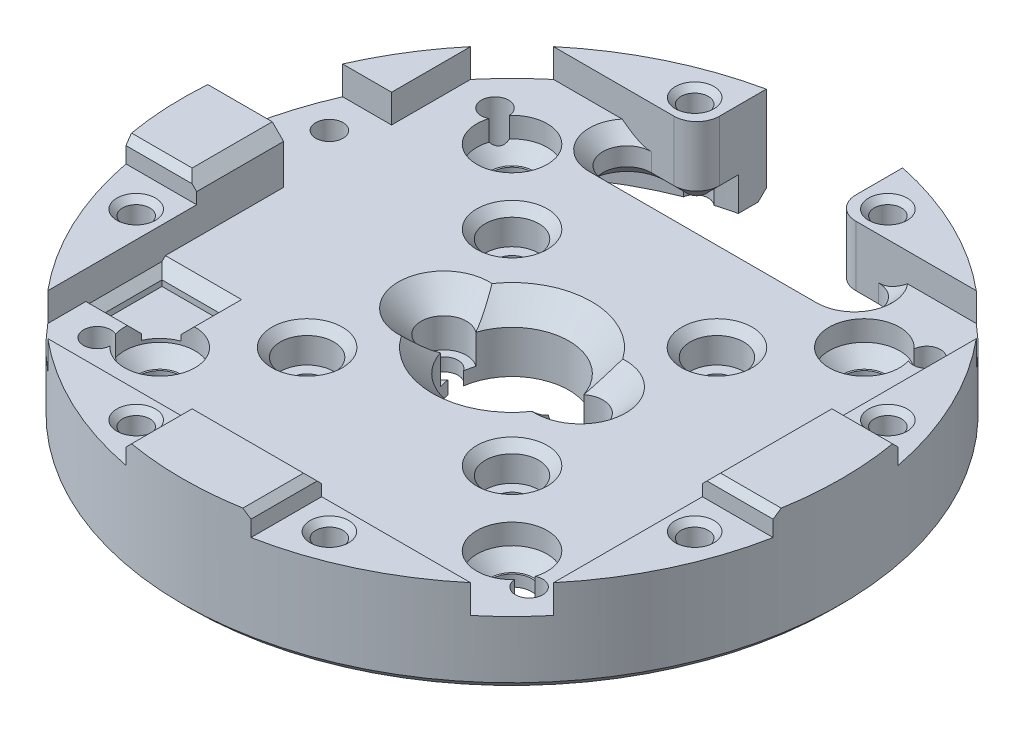
SolidWorks part; units mm, degrees
ref_plane "Front Plane" through (0, 0, 0) normal (0, 0, 1) x (1, 0, 0)
ref_plane "Top Plane" through (0, 0, 0) normal (0, 1, 0) x (1, 0, 0)
ref_plane "Right Plane" through (0, 0, 0) normal (1, 0, 0) x (0, 0, -1)
sketch "Sketch1" plane through (0, 0, 0) normal (0, 1, 0) x (1, 0, 0)
  circle A0 centre (0, 0) radius 8.75
  arc A1 (-4.9531, -0.683) -> (4.9531, -0.683) centre (0, 0) ccw
  circle A2 centre (0, 0) radius 6 construction
  arc A3 (-4.9531, 0.683) -> (-4.9531, -0.683) centre (-6, 0) ccw
  arc A4 (4.9531, -0.683) -> (4.9531, 0.683) centre (6, 0) ccw
  arc A5 (4.9531, 0.683) -> (-4.9531, 0.683) centre (0, 0) ccw
  dimension "D1" = 17.5
  dimension "D2" = 10
  dimension "D3" = 2.5
  dimension "D4" = 12
extrude "Boss-Extrude1" add sketch "Sketch1" along normal blind 1.75
sketch "Sketch2" plane through (0, 1.75, 0) normal (0, 1, 0) x (1, 0, 0)
  circle A0 centre (-6, 0) radius 2
  circle A1 centre (6, 0) radius 2
  dimension "D1" = 4
extrude "Cut-Extrude1" cut sketch "Sketch2" against normal blind 0.6
sketch "Sketch3" plane through (0, 1.75, 0) normal (0, -1, 0) x (1, 0, 0)
  line L0 (-12.0837, 0) -> (12.0837, 0) construction
  line L1 (-19, -17.5) -> (19, -17.5) construction
  line L2 (-19, -17.5) -> (-19, 17.5) construction
  line L3 (-19, 17.5) -> (19, 17.5) construction
  line L4 (19, -17.5) -> (19, 17.5) construction
  line L5 (-19, -17.5) -> (19, 17.5) construction
  line L6 (-19, 17.5) -> (19, -17.5) construction
  line L11 (-23.4352, -20.7052) -> (23.4352, 20.7052) construction
  line L12 (-23.4352, 20.7052) -> (23.4352, -20.7052) construction
  line L13 (0, 12.2133) -> (0, -11.1132) construction
  circle A0 centre (19, 17.5) radius 1.2
  circle A1 centre (19, -17.5) radius 1.2
  circle A2 centre (-19, -17.5) radius 1.2
  circle A3 centre (-19, 17.5) radius 1.2
  arc A8 (-4.75, -1.5612) -> (4.75, -1.5612) centre (0, 0) ccw
  circle A9 centre (0, 0) radius 5 construction
  arc A10 (-4.75, 1.5612) -> (-4.75, -1.5612) centre (-6, 0) ccw
  arc A11 (4.75, -1.5612) -> (4.75, 1.5612) centre (6, 0) ccw
  circle A12 centre (0, 0) radius 29
  arc A14 (-4.75, 1.5612) -> (-4.75, -1.5612) centre (-6, 0) ccw construction
  arc A15 (4.75, 1.5612) -> (-4.75, 1.5612) centre (0, 0) ccw
  point P0 (0, 0)
  point P6 (0, 0)
  dimension "D3" = 2.4
  dimension "D4" = 58
  dimension "D1" = 35
  dimension "D2" = 38
extrude "Boss-Extrude2" add sketch "Sketch3" against normal blind 6.5
sketch "Sketch4" plane through (0, 8.25, 0) normal (0, 1, 0) x (1, 0, 0)
  line L1 (-22.25, 22.25) -> (22.25, 22.25)
  line L2 (-22.25, 22.25) -> (-22.25, -22.25)
  line L3 (-22.25, -22.25) -> (22.25, -22.25)
  line L4 (22.25, 22.25) -> (22.25, -22.25)
  line L5 (-22.25, 22.25) -> (22.25, -22.25) construction
  line L6 (-22.25, -22.25) -> (22.25, 22.25) construction
  point P0 (0, 0)
  dimension "D1" = 44.5
  dimension "D2" = 44.5
extrude "Cut-Extrude2" cut sketch "Sketch4" against normal blind 2.5
chamfer "Chamfer1" distance 0.5 angle 45 1 edges at (0, 0, 8.75)
chamfer "Chamfer2" distance 2 angle 45 4 edges at (0, 5.75, 5) (8, 5.75, 0) (0, 5.75, -5) (-8, 5.75, 0)
sketch "Sketch10" plane through (0, 1.75, 0) normal (0, -1, 0) x (1, 0, 0)
  circle A0 centre (0, 0) radius 26.6
  circle A1 centre (0, 0) radius 29
  circle A2 centre (0, 0) radius 29 construction
  dimension "D1" = 53.2
extrude "Boss-Extrude3" add sketch "Sketch10" along normal blind 1.75
sketch "Sketch5" plane through (0, 5.75, 0) normal (0, 1, 0) x (1, 0, 0)
  line L0 (15.4998, -15.4998) -> (-15.4998, 15.4998) construction
  line L1 (15.4998, 15.4998) -> (-15.4998, -15.4998) construction
  line L2 (0, 17.5033) -> (0, -11.3042) construction
  circle A0 centre (0, 0) radius 21.92 construction
  circle A1 centre (-15.4998, 15.4998) radius 1.75
  circle A2 centre (15.4998, 15.4998) radius 1.75
  circle A3 centre (15.4998, -15.4998) radius 1.75
  circle A4 centre (-15.4998, -15.4998) radius 1.75
  dimension "D1" = 43.84
  dimension "D3" = 3.5
  dimension "D2" = 45
extrude "Cut-Extrude3" cut sketch "Sketch5" against normal through all
sketch "Sketch7" plane through (0, 8.25, 0) normal (0, 1, 0) x (1, 0, 0)
  line L1 (-6, 42.3425) -> (6, 42.3425)
  line L2 (-6, 42.3425) -> (-6, 18)
  line L3 (-6, 18) -> (6, 18)
  line L4 (6, 42.3425) -> (6, 18)
  line L5 (-6, 42.3425) -> (6, 18) construction
  line L6 (-6, 18) -> (6, 42.3425) construction
  point P0 (0, 30.1713)
  point P5 (0, 0)
  point P7 (0, 24.1805)
  dimension "D1" = 12
  dimension "D2" = 18
extrude "Cut-Extrude5" cut sketch "Sketch7" against normal blind 12
sketch "Sketch11" plane through (0, 5.75, 0) normal (0, 1, 0) x (1, 0, 0)
  line L0 (0, 0) -> (15.4998, 15.4998) construction
  line L1 (0, 0) -> (-15.4998, 15.4998) construction
  line L2 (0, 0) -> (-15.4998, -15.4998) construction
  line L3 (0, 0) -> (15.4998, -15.4998) construction
  circle A0 centre (0, 0) radius 12.75 construction
  circle A1 centre (-9.0156, 9.0156) radius 2.35
  circle A2 centre (9.0156, 9.0156) radius 2.35
  circle A3 centre (9.0156, -9.0156) radius 2.35
  circle A4 centre (-9.0156, -9.0156) radius 2.35
  point P19 (15.4998, 15.4998)
  point P21 (-15.4998, 15.4998)
  point P23 (15.4998, -15.4998)
  point P25 (-15.4998, -15.4998)
  dimension "D1" = 25.5
  dimension "D2" = 4.7
extrude "Cut-Extrude8" cut sketch "Sketch11" against normal blind 3
sketch "Sketch8" plane through (0, 5.75, 0) normal (0, 1, 0) x (1, 0, 0)
  line L0 (-22.25, 18.5994) -> (-22.25, -18.5994) construction
  line L1 (-21.55, -14.25) -> (-16.55, -14.25)
  line L2 (-21.55, -14.25) -> (-21.55, -9.25)
  line L3 (-21.55, -9.25) -> (-16.55, -9.25)
  line L4 (-16.55, -14.25) -> (-16.55, -9.25)
  line L5 (-18.5994, -22.25) -> (18.5994, -22.25) construction
  point P4 (14.0294, 7.1954)
  point P5 (-13.8698, -4.0216)
  point P6 (-12.3881, -2.2225)
  point P7 (-19.0556, -9.1016)
  point P8 (-20.9268, -12.3659)
  point P9 (-15.5073, -6.9048)
  point P10 (-13.81, -13.5108)
  point P11 (-19.7221, -8.0773)
  point P12 (-13.6235, -13.4745)
  point P15 (-15.8156, -14.6243)
  point P16 (-16.1616, -15.0828)
  point P17 (-16.55, -14.8974)
  point P18 (-16.55, -9.4553)
  dimension "D1" = 0.7
  dimension "D2" = 5
  dimension "D3" = 8
extrude "Cut-Extrude6" cut sketch "Sketch8" against normal blind 1.5
sketch "Sketch12" plane through (0, 2.75, 0) normal (0, 1, 0) x (1, 0, 0)
  circle A0 centre (-9.0156, 9.0156) radius 1.4
  circle A1 centre (9.0156, 9.0156) radius 1.4
  circle A2 centre (9.0156, -9.0156) radius 1.4
  circle A3 centre (-9.0156, -9.0156) radius 1.4
  dimension "D1" = 2.8
extrude "Cut-Extrude9" cut sketch "Sketch12" against normal through all
fillet "Fillet2" radius 3 2 edges at (-6, 3.75, -18) (6, 3.75, -18)
chamfer "Chamfer6" distance 0.7 angle 45 1 edges at (0, 0, 29)
sketch "Sketch14" plane through (0, 8.25, 0) normal (0, 1, 0) x (1, 0, 0)
  line L0 (22.25, 5.5) -> (22.25, -5.5)
  line L1 (22.25, -18.5994) -> (22.25, 18.5994) construction
  line L2 (22.25, -5.5) -> (28.4737, -5.5)
  line L3 (22.25, 5.5) -> (28.4737, 5.5)
  line L4 (5.5, -22.25) -> (-5.5, -22.25)
  line L5 (-5.5, -22.25) -> (-5.5, -28.4737)
  line L6 (5.5, -22.25) -> (5.5, -28.4737)
  line L7 (-22.25, -5.5) -> (-22.25, 5.5)
  line L8 (-22.25, 5.5) -> (-28.4737, 5.5)
  line L9 (-22.25, -5.5) -> (-28.4737, -5.5)
  arc A0 (28.4737, -5.5) -> (28.4737, 5.5) centre (0, 0) ccw
  arc A1 (22.25, -18.5994) -> (22.25, 18.5994) centre (0, 0) ccw construction
  arc A2 (-5.5, -28.4737) -> (5.5, -28.4737) centre (0, 0) ccw
  arc A3 (-28.4737, 5.5) -> (-28.4737, -5.5) centre (0, 0) ccw
  point P10 (22.25, 0)
  point P22 (0, 0)
  dimension "D2" = 11
  dimension "D1" = 3
extrude "Boss-Extrude5" add sketch "Sketch14" along normal blind 2
sketch "Sketch15" plane through (0, 8.25, 0) normal (0, 1, 0) x (1, 0, 0)
  circle A0 centre (0, 0) radius 26 construction
  circle A1 centre (24.5713, 8.5) radius 1.2
  circle A2 centre (24.5713, -8.5) radius 1.2
  circle A3 centre (8.5, -24.5713) radius 1.2
  circle A4 centre (-8.5, -24.5713) radius 1.2
  circle A5 centre (-24.5713, -8.5) radius 1.2
  circle A6 centre (-24.5713, 8.5) radius 1.2
  circle A7 centre (-8.5, 24.5713) radius 1.2
  circle A8 centre (8.5, 24.5713) radius 1.2
  point P22 (0, 0)
  dimension "D2" = 52
  dimension "D3" = 2.4
  dimension "D1" = 17
  dimension "D4" = 4
extrude "Cut-Extrude10" cut sketch "Sketch15" against normal through all
chamfer "Chamfer7" distance 0.75 angle 45 4 edges at (-9.0156, 5.75, -6.6656) (-9.0156, 5.75, 11.3656) (9.0156, 5.75, 11.3656) (9.0156, 5.75, -6.6656)
sketch "Sketch9" plane through (0, 8.25, 0) normal (0, 1, 0) x (1, 0, 0)
  line L1 (-35.229, 11.65) -> (-19.1435, 11.65)
  line L2 (-35.229, 11.65) -> (-35.229, 2.15)
  line L3 (-35.229, 2.15) -> (-19.1435, 2.15)
  line L4 (-19.1435, 11.65) -> (-19.1435, 2.15)
  dimension "D1" = 9.5
  dimension "D2" = 2.15
extrude "Cut-Extrude7" cut sketch "Sketch9" against normal up to surface (2.5 mm away) from offset 5 up to face at (-9.0156, 5.75, -5.9156)
sketch "Sketch16" plane through (0, 5.75, 0) normal (0, 1, 0) x (1, 0, 0)
  circle A0 centre (-15.4998, 15.4998) radius 3.1
  circle A1 centre (15.4998, 15.4998) radius 3.1
  circle A2 centre (15.4998, -15.4998) radius 3.1
  circle A3 centre (-15.4998, -15.4998) radius 3.1
  dimension "D1" = 6.2
extrude "Cut-Extrude11" cut sketch "Sketch16" against normal blind 3
chamfer "Chamfer8" distance 1.2 angle 45 4 edges at (-12.8083, 2.75, -13.9617) (-12.8083, 2.75, 13.9617) (12.8083, 2.75, 13.9617) (12.8083, 2.75, -13.9617)
chamfer "Chamfer9" distance 0.5 angle 45 7 edges at (-8.5, 8.25, 25.7713) (8.5, 8.25, 25.7713) (-24.5713, 8.25, 9.7) (-8.5, 8.25, -23.3713) (8.5, 8.25, -23.3713) (24.5713, 8.25, 9.7) (24.5713, 8.25, -7.3)
chamfer "Chamfer10" distance 1 angle 45 4 edges at (-16.55, 5.75, 10.9165) (-19.9433, 5.75, 14.25) (-21.55, 5.75, 11.75) (-19.05, 5.75, 9.25)
chamfer "Chamfer11" distance 1 angle 45 3 edges at (22.25, 10.25, 0) (-22.25, 10.25, 1.675) (0, 10.25, 22.25)
sketch "Sketch17" plane through (0, 5.75, 0) normal (0, 1, 0) x (1, 0, 0)
  line L0 (-10, 20.125) -> (10, 20.125) construction
  line L1 (-10, 22.25) -> (10, 22.25)
  line L2 (-10, 18) -> (10, 18)
  line L3 (-3, 18) -> (3, 18) construction
  line L4 (18.5994, 22.25) -> (6, 22.25) construction
  arc A0 (-10, 22.25) -> (-10, 18) centre (-10, 20.125) ccw
  arc A1 (10, 18) -> (10, 22.25) centre (10, 20.125) ccw
  point P2 (0, 20.125)
  point P11 (0, 0)
  dimension "D1" = 20
extrude "Cut-Extrude12" cut sketch "Sketch17" against normal through all
fillet "Fillet3" radius 2 2 edges at (6, 5, -22.25) (-6, 5, -22.25)
chamfer "Chamfer12" distance 1.2 angle 45 12 edges at (-6, 1.75, -25.0822) (0, 1.75, -18) (6, 1.75, -25.0822) (0, 5.75, -18) (-12.125, 5.75, -20.125) (12.125, 5.75, -20.125) (6.5858, 1.75, -22.8358) (-6.5858, 1.75, -22.8358) (9, 1.75, -22.25) (-9, 1.75, -22.25) (12.125, 1.75, -20.125) (-12.125, 1.75, -20.125)
chamfer "Chamfer13" distance 0.6 angle 45 5 edges at (25.8618, 10.25, -5.5) (25.8618, 10.25, 5.5) (5.5, 10.25, 25.8618) (-5.5, 10.25, 25.8618) (-25.8618, 10.25, 5.5)
